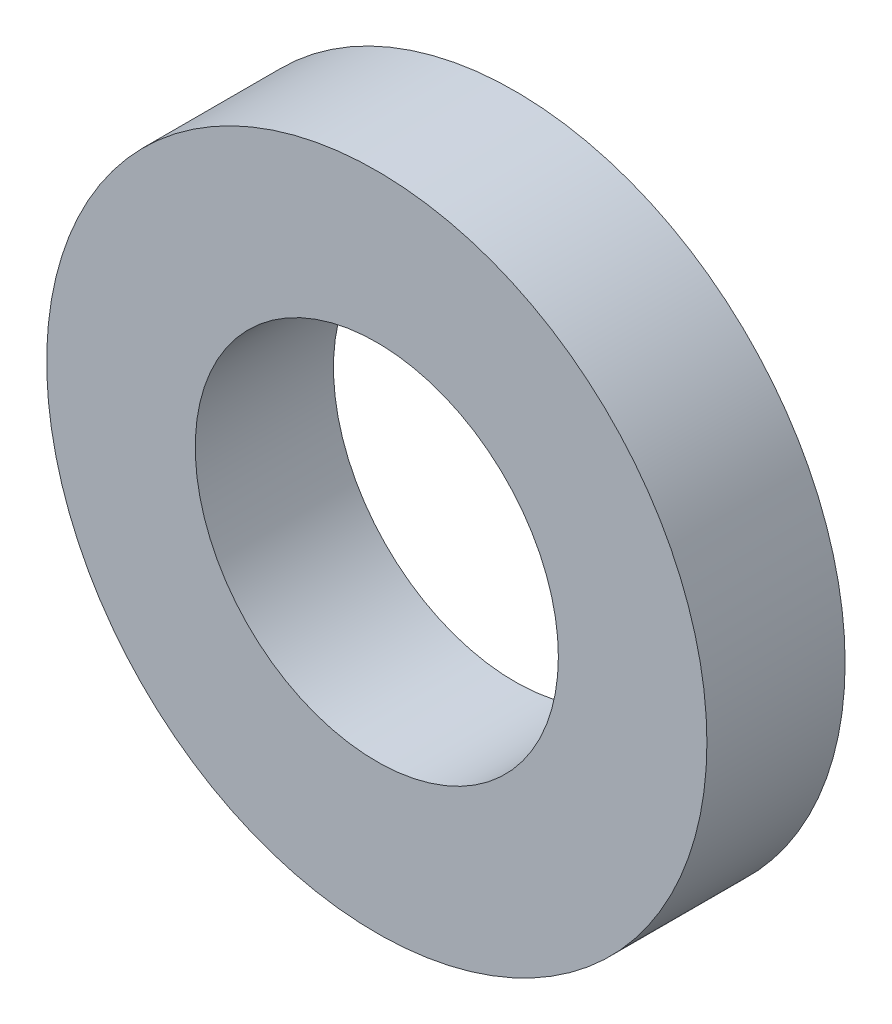
SolidWorks part; units mm, degrees
material "Nylon 101"
ref_plane "Front Plane" through (0, 0, 0) normal (0, 0, 1) x (1, 0, 0)
ref_plane "Top Plane" through (0, 0, 0) normal (0, 1, 0) x (1, 0, 0)
ref_plane "Right Plane" through (0, 0, 0) normal (1, 0, 0) x (0, 0, -1)
sketch "Sketch1" plane through (0, 0, 0) normal (0, 0, 1) x (1, 0, 0)
  circle A0 centre (0, 0) radius 9.525
  circle A1 centre (0, 0) radius 5.2387
  dimension "D1" = 19.05
  dimension "D2" = 10.4775
extrude "Boss-Extrude1" add sketch "Sketch1" along normal mid plane 3.9875
equation "\"D1@Boss-Extrude1\"=0.0625in+0.45mm/2"
